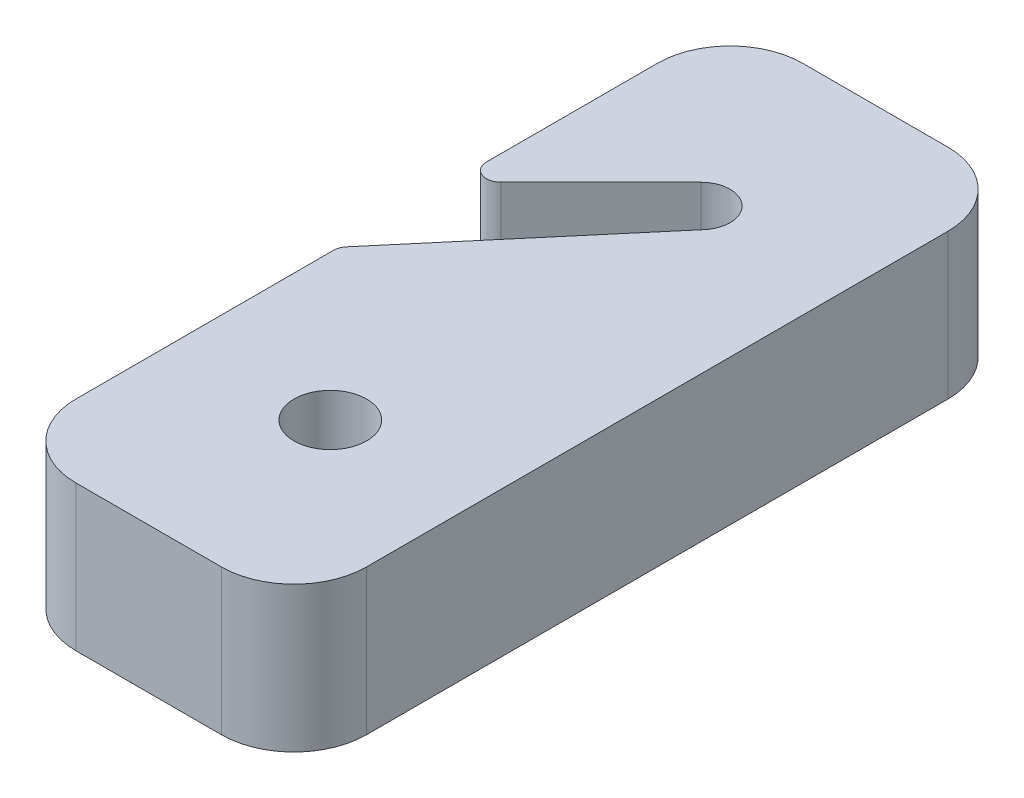
SolidWorks part; units mm, degrees
ref_plane "Front Plane" through (0, 0, 0) normal (0, 0, 1) x (1, 0, 0)
ref_plane "Top Plane" through (0, 0, 0) normal (0, 1, 0) x (1, 0, 0)
ref_plane "Right Plane" through (0, 0, 0) normal (1, 0, 0) x (0, 0, -1)
sketch "Sketch1" plane through (0, 0, 0) normal (0, 1, 0) x (1, 0, 0)
  line L0 (0, 0) -> (0, 50000) construction
  line L1 (6.35, -15.875) -> (-6.35, -15.875)
  line L2 (6.35, -15.875) -> (6.35, 15.875)
  line L3 (6.35, 15.875) -> (-6.35, 15.875)
  line L4 (-6.35, -15.875) -> (-6.35, 15.875)
  line L5 (6.35, -15.875) -> (-6.35, 15.875) construction
  line L6 (6.35, 15.875) -> (-6.35, -15.875) construction
  line L7 (-0.898, 9.153) -> (-6.35, 3.7011)
  line L8 (0.9694, 7.4345) -> (-6.35, -1.2135)
  circle A0 centre (0, -7.9375) radius 1.5875
  circle A1 centre (0, 8.255) radius 1.27
  point P0 (0, 0)
  point P12 (0, 9.525)
  point P13 (0, -9.525)
  point P18 (-1.0981, 9.0839)
  dimension "D1" = 12.7
  dimension "D2" = 31.75
  dimension "D8" = 3.175
  dimension "D3" = 2.54
  dimension "D4" = 3.175
  dimension "D5" = 6.35
  dimension "D6" = 6.35
  dimension "D7" = 45
extrude "Boss-Extrude2" add sketch "Sketch1" along normal blind 6.35 contours A0 | A1 L7 L4 L8 | A1 | L3 L4 L1 L2 region at (-3.5812, 0, -4.1675) region at (0, 0, -8.255) region at (0, 0, 7.9375)
extrude "Cut-Extrude2" cut sketch "Sketch1<5>" along normal through all contours A1 L7 L4 L8 | A1 region at (-3.5812, 0, -4.1675) region at (0, 0, -8.255)
sketch "Sketch1<5>" plane through (0, 0, 0) normal (0, 1, 0) x (1, 0, 0) same geometry as "Sketch1"
fillet "Fillet2" radius 3.175 4 edges at (-6.35, 3.175, -15.875) (6.35, 3.175, -15.875) (6.35, 3.175, 15.875) (-6.35, 3.175, 15.875)
fillet "Fillet3" radius 0.635 2 edges at (-6.35, 3.175, 1.2135) (-6.35, 3.175, -3.7011)
